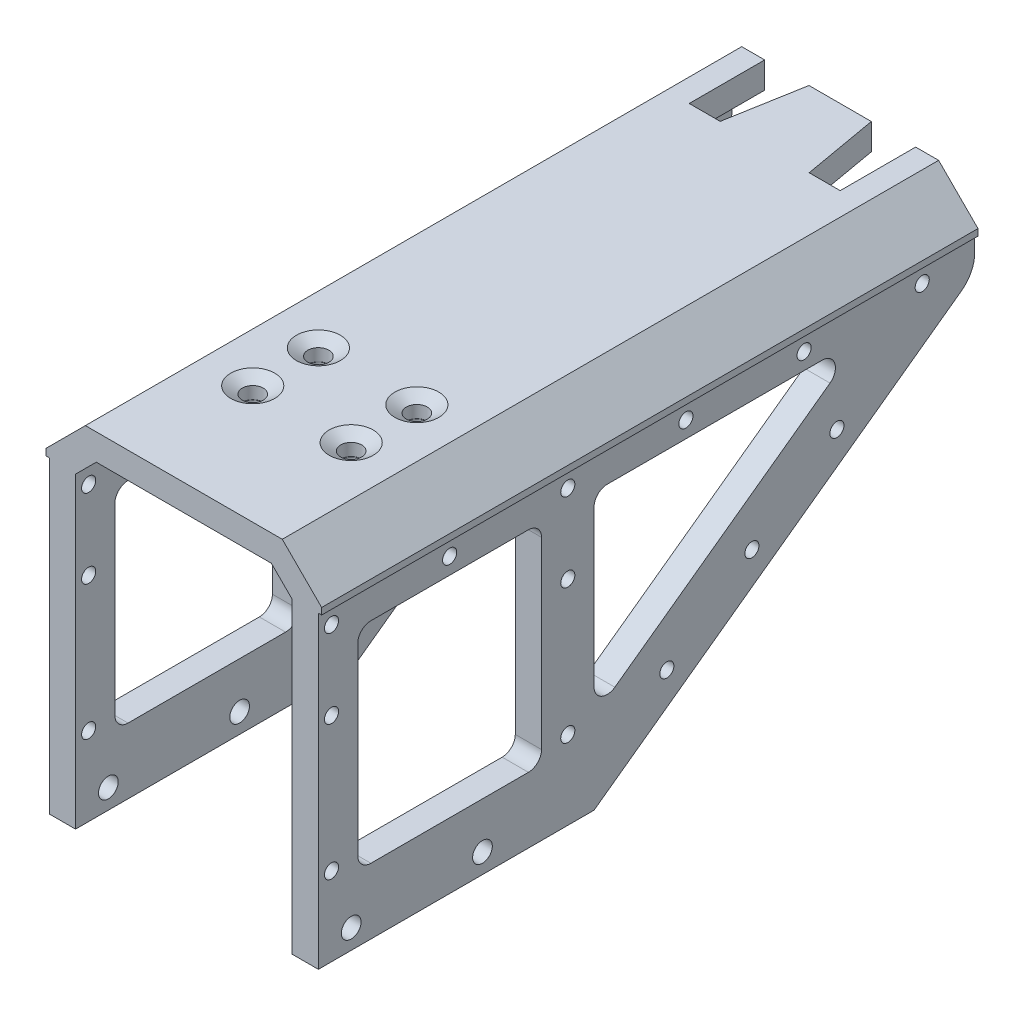
SolidWorks part; units mm, degrees
material "尼龙 101"
ref_plane "Front" through (0, 0, 0) normal (0, 0, 1) x (1, 0, 0)
ref_plane "Top" through (0, 0, 0) normal (0, 1, 0) x (1, 0, 0)
ref_plane "Right" through (0, 0, 0) normal (1, 0, 0) x (0, 0, -1)
sketch "草图1" plane through (0, 0, 0) normal (0, 0, 1) x (1, 0, 0)
  line L0 (0, 22.6301) -> (0, -19.2329) construction
  line L1 (-15, 0) -> (15, 0)
  line L3 (20.5, -54) -> (16.5, -54)
  line L5 (13.3431, -4) -> (-13.3431, -4)
  line L10 (16.5, -7.1569) -> (16.5, -54)
  line L12 (20.5, -7) -> (20.5, -54)
  line L18 (15, 0) -> (21, -6)
  line L19 (13.3431, -4) -> (16.5, -7.1569)
  line L20 (20.5, -7) -> (21, -7)
  line L21 (21, -7) -> (21, -6)
  line L22 (-21, -7) -> (-21, -6)
  line L23 (-20.5, -7) -> (-21, -7)
  line L24 (-13.3431, -4) -> (-16.5, -7.1569)
  line L25 (-15, 0) -> (-21, -6)
  line L26 (-20.5, -7) -> (-20.5, -54)
  line L27 (-16.5, -7.1569) -> (-16.5, -54)
  line L29 (-20.5, -54) -> (-16.5, -54)
  point P5 (0, 0)
  point P24 (0, -4)
  dimension "D5" = 4
  dimension "D6" = 4
  dimension "D1" = 47
  dimension "D2" = 0.5
  dimension "D3" = 50
  dimension "D4" = 15
  dimension "D7" = 135
  dimension "D8" = 4
  dimension "D9" = 16.5
extrude "凸台-拉伸1" add sketch "草图1" along normal mid plane 100
sketch "草图3" plane through (20.5, 0, 0) normal (1, 0, 0) x (0, 0, -1)
  line L0 (-8, -54) -> (50, -12)
  line L1 (-50, -54) -> (50, -54) construction
  line L2 (50, -54) -> (50, -7) construction
  line L3 (50, -12) -> (50, -54)
  line L4 (50, -54) -> (-8, -54)
  line L5 (-50, -54) -> (-50, -7) construction
  line L6 (-8, -41.6534) -> (-8, -54) construction
  line L17 (-50, -44) -> (50, -44)
  line L18 (-44, -44) -> (-16, -44)
  line L23 (-8, -41.6534) -> (32.95, -12)
  line L24 (-44, -54) -> (-44, -7)
  line L25 (-44, -44) -> (-44, -12)
  line L27 (-13.8651, -45.9006) -> (44.1349, -3.9006) construction
  line L28 (-50, -12) -> (50, -12)
  line L29 (-44, -12) -> (-16, -12)
  line L30 (-16, -44) -> (-16, -12)
  line L31 (-8, -41.6534) -> (-8, -12)
  line L32 (-8, -12) -> (32.95, -12)
  dimension "D1" = 42
  dimension "D2" = 5
  dimension "D7" = 8
  dimension "D3" = 10
  dimension "D4" = 6
  dimension "D5" = 10
  dimension "D6" = 5
extrude "切除-拉伸2" cut sketch "草图3" against normal through all
sketch "草图4" plane through (20.5, 0, 0) normal (1, 0, 0) x (0, 0, -1)
  line L0 (-50, -54) -> (-8, -54) construction
  line L1 (-50, -54) -> (-50, -7) construction
  line L2 (-50, -7) -> (50, -7) construction
  line L3 (50, -12) -> (-8, -54) construction
  line L4 (-30, -9.5) -> (-30, -50009.5) construction
  line L12 (-47, -51) -> (-8.9721, -51)
  line L13 (-8.9721, -51) -> (47, -10.4684)
  line L14 (47, -10.4684) -> (47, -10)
  line L15 (47, -10) -> (-47, -10)
  line L16 (-47, -10) -> (-47, -51)
  line L17 (-48, -51) -> (-10.6771, -51) construction
  line L33 (-10.6771, -51) -> (46.6324, -9.5) construction
  line L35 (46.6324, -9.5) -> (-48, -9.5) construction
  line L36 (-48, -9.5) -> (-48, -51) construction
  circle A0 centre (-45, -51) radius 1.5
  circle A1 centre (-25, -51) radius 1.5
  circle A2 centre (-48, -42) radius 1.075
  circle A3 centre (-48, -21.5) radius 1.075
  circle A4 centre (-48, -9.5) radius 1.075
  circle A12 centre (3.0919, -41.0293) radius 1.075
  circle A17 centre (-30, -9.5) radius 1.075
  circle A18 centre (-12, -9.5) radius 1.075
  circle A24 centre (6, -9.5) radius 1.075
  circle A27 centre (24, -9.5) radius 1.075
  circle A28 centre (42, -9.5) radius 1.075
  circle A29 centre (-12, -21.5) radius 1.075
  circle A30 centre (-12, -42) radius 1.075
  circle A31 centre (16.0509, -31.6452) radius 1.075
  circle A32 centre (29.01, -22.261) radius 1.075
  dimension "D1" = 3
  dimension "D2" = 3
  dimension "D3" = 5
  dimension "D4" = 20
  dimension "D5" = 3
  dimension "D7" = 2
  dimension "D10" = 6
  dimension "D11" = 9
  dimension "D12" = 3
  dimension "D14" = 2.15
  dimension "D16" = 16
  dimension "D18" = 17
  dimension "D8" = 2.5
  dimension "D9" = 4
  dimension "D13" = 12
  dimension "D15" = 18
  dimension "D6" = 3
extrude "切除-拉伸3" cut sketch "草图4" against normal through all
fillet "圆角1" radius 2 14 edges at (18.5, -12, -32.95) (18.5, -12, 16) (18.5, -12, 44) (18.5, -44, 44) (18.5, -44, 16) (18.5, -41.6534, 8) (-18.5, -12, 16) (18.5, -12, 8) (-18.5, -12, 8) (-18.5, -12, -32.95) (-18.5, -41.6534, 8) (-18.5, -12, 44) (-18.5, -44, 44) (-18.5, -44, 16)
sketch "草图8" plane through (20.5, 0, 0) normal (1, 0, 0) x (0, 0, -1)
  line L7 (-50, -18.6277) -> (-50, -24.3723)
  line L8 (-50, -7) -> (-50, -54) construction
  line L9 (-50, -39.1277) -> (-50, -44.8723)
  circle A7 centre (-48, -21.5) radius 1.5
  circle A9 centre (-48, -42) radius 1.5
  circle A10 centre (-12, -21.5) radius 3.5
  circle A11 centre (-12, -21.5) radius 1.5
  circle A12 centre (-12, -42) radius 3.5
  circle A13 centre (-12, -42) radius 1.5
  arc A20 (-50, -24.3723) -> (-50, -18.6277) centre (-48, -21.5) ccw
  arc A21 (-50, -44.8723) -> (-50, -39.1277) centre (-48, -42) ccw
  dimension "D2" = 7
  dimension "D3" = 3
  dimension "D4" = 7
  dimension "D5" = 3
  dimension "D6" = 7
  dimension "D7" = 3
  dimension "D8" = 3
  dimension "D15" = 7
extrude "凸台-拉伸4" add sketch "草图8" against normal blind 4
mirror "镜向2" about plane through (0, 0, 0) normal (1, 0, 0) of "凸台-拉伸4"
fillet "圆角4" radius 5 2 edges at (18.5, -12, -50) (-18.5, -12, -50)
sketch "草图10" plane through (0, 0, 0) normal (0, 1, 0) x (1, 0, 0)
  line L0 (-4.75, 50) -> (-6.7778, 38.5)
  line L1 (15, 50) -> (-15, 50) construction
  line L2 (-6.7778, 38.5) -> (-11.5, 38.5)
  line L3 (-11.5, 38.5) -> (-11.5, 50)
  line L4 (-11.5, 50) -> (-4.75, 50)
  line L5 (0, 50) -> (0, -49950) construction
  line L6 (11.5, 50) -> (4.75, 50)
  line L7 (11.5, 38.5) -> (11.5, 50)
  line L8 (6.7778, 38.5) -> (11.5, 38.5)
  line L9 (4.75, 50) -> (6.7778, 38.5)
  point P8 (0, 50)
  dimension "D1" = 9.5
  dimension "D2" = 100
  dimension "D3" = 23
  dimension "D4" = 11.5
extrude "切除-拉伸5" cut sketch "草图10" against normal blind 10
fillet "圆角7" [suppressed] radius 2
sketch "草图11" plane through (0, -4, 0) normal (0, -1, 0) x (1, 0, 0)
  line L0 (0, -10) -> (0, -20) construction
  line L1 (10, -10) -> (10, -20)
  line L2 (-10, -10) -> (-10, -20)
  line L3 (0, 30) -> (0, 20) construction
  line L4 (10, 30) -> (10, 20)
  line L5 (-10, 30) -> (-10, 20)
  arc A1 (10, -10) -> (-10, -10) centre (0, -10) ccw
  arc A2 (-10, -20) -> (10, -20) centre (0, -20) ccw
  arc A3 (10, 30) -> (-10, 30) centre (0, 30) ccw
  arc A4 (-10, 20) -> (10, 20) centre (0, 20) ccw
  point P2 (0, -15)
  point P8 (0, 25)
  dimension "D1" = 10
  dimension "D2" = 10
  dimension "D3" = 10
  dimension "D4" = 10
  dimension "D5" = 15
  dimension "D6" = 40
extrude "切除-拉伸6" [suppressed] cut sketch "草图11" against normal blind 2
fillet "圆角8" [suppressed] radius 1
sketch "草图12" plane through (0, 0, 0) normal (0, 1, 0) x (1, 0, 0)
  line L0 (15, -50) -> (-15, -50) construction
  line L1 (0, 0) -> (0, -58.0372) construction
  line L2 (-7.5, -32) -> (7.5, -32) construction
  line L3 (-7.5, -32) -> (-7.5, -22) construction
  line L4 (-7.5, -22) -> (7.5, -22) construction
  line L5 (7.5, -32) -> (7.5, -22) construction
  circle A0 centre (-7.5, -32) radius 1.6
  circle A1 centre (7.5, -32) radius 1.6
  circle A2 centre (7.5, -22) radius 1.6
  circle A3 centre (-7.5, -22) radius 1.6
  dimension "D1" = 18
  dimension "D4" = 3.2
  dimension "D2" = 10
  dimension "D3" = 15
extrude "切除-拉伸7" cut sketch "草图12" against normal through all
ref_plane "基准面1" through (0, -3, 0) normal (0, 1, 0) x (1, 0, 0)
sketch "草图13" plane through (0, 0, 0) normal (0, 1, 0) x (1, 0, 0)
  circle A0 centre (-7.5, -22) radius 3.35
  circle A1 centre (7.5, -22) radius 3.35
  circle A2 centre (-7.5, -32) radius 3.35
  circle A3 centre (7.5, -32) radius 3.35
  dimension "D1" = 6.7
sketch "草图14" plane through (0, -3, 0) normal (0, 1, 0) x (1, 0, 0)
  circle A0 centre (-7.5, -22) radius 1.65
  circle A1 centre (-7.5, -32) radius 1.65
  circle A2 centre (7.5, -32) radius 1.65
  circle A3 centre (7.5, -22) radius 1.65
  dimension "D1" = 3.3
loft "切除-放样1" cut section "草图13" section "草图14" start constraint default connector at (-10.0073, 0, 19.7783) connector at (-6.8533, -3, 23.518)
pattern_linear "阵列(线性)1" count 2 spacing 15 along (1, 0, 0) of "切除-放样1"
pattern_linear "阵列(线性)2" count 2 spacing 10 along (0, 0, 1) of "阵列(线性)1"
fillet "圆角9" [suppressed] radius 2.4
fillet "圆角10" [suppressed] radius 2.5
fillet "圆角11" [suppressed] radius 1.5
sketch "草图15" plane through (0, 0, 50) normal (0, 0, 1) x (1, 0, 0)
  line L0 (-16.5, -54) -> (-20.5, -54)
  line L1 (-20.5, -54) -> (-20.5, -7)
  line L2 (-20.5, -7) -> (-21, -7)
  line L3 (-21, -7) -> (-21, -6)
  line L4 (-21, -6) -> (-15, 0)
  line L5 (-15, 0) -> (15, 0)
  line L6 (15, 0) -> (21, -6)
  line L7 (21, -6) -> (15, 0) construction
  line L8 (21, -6) -> (21, -7)
  line L9 (21, -7) -> (20.5, -7)
  line L10 (20.5, -7) -> (20.5, -54)
  line L11 (20.5, -54) -> (20.5, -7) construction
  line L12 (20.5, -54) -> (16.5, -54)
  line L13 (16.5, -54) -> (16.5, -7.1569)
  line L14 (16.5, -7.1569) -> (13.3431, -4)
  line L15 (13.3431, -4) -> (-13.3431, -4)
  line L16 (-13.3431, -4) -> (-16.5, -7.1569)
  line L17 (-16.5, -7.1569) -> (-16.5, -54)
  line L18 (-15, 0) -> (-21, -6) construction
  dimension "D1" = 30
  dimension "D2" = 42
  dimension "D3" = 6
sketch "草图16" plane through (20.5, 0, 0) normal (1, 0, 0) x (0, 0, -1)
  line L0 (-42, -12) -> (-18, -12)
  line L1 (-44, -14) -> (-44, -42)
  line L2 (-42, -44) -> (-18, -44)
  line L3 (-16, -14) -> (-16, -42)
  line L4 (-16, -42) -> (-16, -14) construction
  line L5 (50, -9.4474) -> (50, -7)
  line L6 (50, -7) -> (-50, -7)
  line L7 (-50, -7) -> (-50, -54)
  line L8 (-50, -54) -> (-8, -54)
  line L9 (-8, -54) -> (47.9325, -13.4971)
  line L10 (50, -9.4474) -> (50, -7)
  line L11 (50, -7) -> (-50, -7)
  line L12 (-50, -7) -> (-50, -54)
  line L13 (-50, -54) -> (-8, -54)
  line L14 (-8, -54) -> (47.9325, -13.4971)
  line L15 (-8, -14) -> (-8, -37.7359)
  line L16 (-4.827, -39.3557) -> (27.9511, -15.6199)
  line L17 (-6, -12) -> (26.7781, -12)
  arc A0 (-44, -14) -> (-42, -12) centre (-42, -14) cw
  arc A1 (47.9325, -13.4971) -> (50, -9.4474) centre (45, -9.4474) ccw
  arc A2 (47.9325, -13.4971) -> (50, -9.4474) centre (45, -9.4474) ccw
  arc A3 (-18, -12) -> (-16, -14) centre (-18, -14) cw
  arc A4 (-44, -42) -> (-42, -44) centre (-42, -42) ccw
  arc A5 (-18, -44) -> (-16, -42) centre (-18, -42) ccw
  arc A6 (-6, -12) -> (-8, -14) centre (-6, -14) ccw
  arc A7 (26.7781, -12) -> (27.9511, -15.6199) centre (26.7781, -14) cw
  arc A8 (-8, -37.7359) -> (-4.827, -39.3557) centre (-6, -37.7359) ccw
  circle A9 centre (-48, -9.5) radius 1.075
  circle A10 centre (-30, -9.5) radius 1.075
  circle A11 centre (-12, -9.5) radius 1.075
  circle A12 centre (6, -9.5) radius 1.075
  circle A13 centre (24, -9.5) radius 1.075
  circle A14 centre (42, -9.5) radius 1.075
  circle A15 centre (29.01, -22.261) radius 1.075
  circle A16 centre (16.0509, -31.6452) radius 1.075
  circle A17 centre (3.0919, -41.0293) radius 1.075
  circle A18 centre (-12, -42) radius 1.075
  circle A19 centre (-12, -21.5) radius 1.075
  circle A20 centre (-25, -51) radius 1.5
  circle A21 centre (-45, -51) radius 1.5
  circle A25 centre (-48, -42) radius 1.075
  circle A26 centre (-48, -21.5) radius 1.075
  dimension "D2" = 2.15
  dimension "D3" = 3
  dimension "D1" = 0
sketch "草图17" [suppressed] plane through (0, 0, 50) normal (0, 0, 1) x (1, 0, 0)
  line L0 (0, 0) -> (-14.0059, 0)
  line L1 (-17.0029, -0.7029) -> (-22.3, -6)
  line L2 (-15.7029, -0.7029) -> (-21, -6)
  line L3 (-21, -6) -> (-21, -7)
  line L4 (-21, -7) -> (-20.5, -7)
  line L5 (-20.5, -7) -> (-20.5, -54)
  line L6 (-20.5, -54) -> (-16.5, -54)
  line L7 (-16.5, -54) -> (-16.5, -7.1569)
  line L8 (-16.5, -7.1569) -> (-13.3431, -4)
  line L9 (-13.3431, -4) -> (13.3431, -4)
  line L10 (13.3431, -4) -> (16.5, -7.1569)
  line L11 (16.5, -7.1569) -> (16.5, -54)
  line L12 (16.5, -54) -> (20.5, -54)
  line L13 (20.5, -54) -> (20.5, -7)
  line L14 (20.5, -7) -> (21, -7)
  line L15 (21, -7) -> (21, -6)
  line L16 (21, -7) -> (21, -6) construction
  line L17 (21, -6) -> (15.7029, -0.7029)
  line L18 (0, 0) -> (14.0059, 0)
  line L19 (-15.3059, 0) -> (-14.0059, 0)
  line L20 (-22.3, -6) -> (-22.3, -7)
  line L21 (-22.3, -7) -> (-21.8, -7)
  line L22 (-21.8, -7) -> (-21.8, -54)
  line L23 (-21.8, -54) -> (-20.5, -54)
  line L24 (0, 0) -> (0, -58.8568) construction
  line L25 (-15.7029, -0.7029) -> (-15, 0) construction
  line L26 (21.8, -54) -> (20.5, -54)
  line L27 (22.3, -7) -> (21.8, -7)
  line L28 (21.8, -7) -> (21.8, -54)
  line L29 (22.3, -6) -> (22.3, -7)
  line L30 (17.0029, -0.7029) -> (22.3, -6)
  line L31 (15.3059, 0) -> (14.0059, 0)
  arc A0 (-15.7029, -0.7029) -> (-14.0059, 0) centre (-14.0059, -2.4) cw
  arc A1 (14.0059, 0) -> (15.7029, -0.7029) centre (14.0059, -2.4) cw
  arc A2 (17.0029, -0.7029) -> (15.3059, 0) centre (15.3059, -2.4) ccw
  arc A3 (-15.3059, 0) -> (-17.0029, -0.7029) centre (-15.3059, -2.4) ccw
  point P56 (16.3, 0)
  point P59 (-16.3, 0)
  arc M29 (-14.0059, 0) -> (-15.7029, -0.7029) centre (-14.0059, -2.4) ccw
  line M30 (-15.7029, -0.7029) -> (-21, -6)
  line M31 (-21, -6) -> (-21, -7)
  line M32 (-21, -7) -> (-20.5, -7)
  line M33 (-20.5, -7) -> (-20.5, -54)
  line M41 (20.5, -54) -> (20.5, -7)
  line M42 (20.5, -7) -> (21, -7)
  line M43 (21, -7) -> (21, -6)
  line M44 (21, -6) -> (15.7029, -0.7029)
  arc M45 (15.7029, -0.7029) -> (14.0059, 0) centre (14.0059, -2.4) ccw
  dimension "D3" = 2.4
  dimension "D1" = 1.3
  dimension "D2" = 1.3
extrude "凸台-拉伸5" [suppressed] add sketch "草图17" against normal up to surface (100 mm away) contours L19 A3 L1 L20 L21 L22 L23 M33 M32 M31 M30 M29 | L30 A2 L31 L26 L28 L27 L29 M45 M44 M43 M42 M41 up to face at (-16.7343, -5.4052, -50)
sketch "草图18" [suppressed] plane through (21.8, 0, 0) normal (1, 0, 0) x (0, 0, -1)
  line L0 (47.9325, -13.4971) -> (-8, -54)
  line L1 (-8, -54) -> (50, -54)
  line L2 (50, -54) -> (50, -9.4474)
  arc A0 (47.9325, -13.4971) -> (50, -9.4474) centre (45, -9.4474) ccw
extrude "切除-拉伸8" [suppressed] cut sketch "草图18" against normal through all
sketch "草图19" [suppressed] plane through (21.8, 0, 0) normal (1, 0, 0) x (0, 0, -1)
  line L0 (-42, -12) -> (-18, -12)
  line L1 (-44, -14) -> (-44, -42)
  line L2 (-42, -44) -> (-18, -44)
  line L3 (-16, -14) -> (-16, -42)
  line L4 (-8, -14) -> (-8, -37.7359)
  line L5 (-4.827, -39.3557) -> (27.9511, -15.6199)
  line L6 (-6, -12) -> (26.7781, -12)
  arc A0 (-44, -14) -> (-42, -12) centre (-42, -14) cw
  arc A1 (-44, -42) -> (-42, -44) centre (-42, -42) ccw
  arc A2 (-18, -44) -> (-16, -42) centre (-18, -42) ccw
  arc A3 (-18, -12) -> (-16, -14) centre (-18, -14) cw
  arc A4 (-8, -14) -> (-6, -12) centre (-6, -14) cw
  arc A5 (-8, -37.7359) -> (-4.827, -39.3557) centre (-6, -37.7359) ccw
  arc A6 (26.7781, -12) -> (27.9511, -15.6199) centre (26.7781, -14) cw
  circle A7 centre (-48, -9.5) radius 1.075
  circle A8 centre (-48, -21.5) radius 1.075
  circle A9 centre (-48, -42) radius 1.075
  circle A10 centre (-45, -51) radius 1.5
  circle A11 centre (-25, -51) radius 1.5
  circle A12 centre (-12, -42) radius 1.075
  circle A13 centre (-12, -21.5) radius 1.075
  circle A14 centre (-30, -9.5) radius 1.075
  circle A15 centre (-12, -9.5) radius 1.075
  circle A16 centre (6, -9.5) radius 1.075
  circle A17 centre (24, -9.5) radius 1.075
  circle A18 centre (29.01, -22.261) radius 1.075
  circle A19 centre (42, -9.5) radius 1.075
  circle A20 centre (16.0509, -31.6452) radius 1.075
  circle A21 centre (3.0919, -41.0293) radius 1.075
  dimension "D1" = 2.15
  dimension "D2" = 3
extrude "切除-拉伸9" [suppressed] cut sketch "草图19" against normal through all
sketch "草图20" [suppressed] plane through (-21.8, 0, 0) normal (-1, 0, 0) x (0, 0, 1)
  line L5 (-47.9325, -13.4971) -> (8, -54)
  line L6 (8, -54) -> (50, -54)
  line L7 (50, -54) -> (50, -7)
  line L8 (50, -7) -> (-50, -7)
  line L9 (-50, -7) -> (-50, -9.4474)
  line L10 (-47.9325, -13.4971) -> (8, -54)
  line L11 (8, -54) -> (50, -54)
  line L12 (50, -54) -> (50, -7)
  line L13 (50, -7) -> (-50, -7)
  line L14 (-50, -7) -> (-50, -9.4474)
  arc A1 (-50, -9.4474) -> (-47.9325, -13.4971) centre (-45, -9.4474) ccw
  arc A2 (-50, -9.4474) -> (-47.9325, -13.4971) centre (-45, -9.4474) ccw
  dimension "D1" = 0
extrude "切除-拉伸10" [suppressed] cut sketch "草图20" against normal blind 1.5
sketch "草图21" [suppressed] plane through (21.8, 0, 0) normal (1, 0, 0) x (0, 0, -1)
  line L5 (-8, -54) -> (47.9325, -13.4971)
  line L6 (50, -9.4474) -> (50, -7)
  line L7 (50, -7) -> (-50, -7)
  line L8 (-50, -7) -> (-50, -54)
  line L9 (-50, -54) -> (-8, -54)
  line L10 (-8, -54) -> (47.9325, -13.4971)
  line L11 (50, -9.4474) -> (50, -7)
  line L12 (50, -7) -> (-50, -7)
  line L13 (-50, -7) -> (-50, -54)
  line L14 (-50, -54) -> (-8, -54)
  arc A1 (47.9325, -13.4971) -> (50, -9.4474) centre (45, -9.4474) ccw
  arc A2 (47.9325, -13.4971) -> (50, -9.4474) centre (45, -9.4474) ccw
  dimension "D1" = 0
extrude "切除-拉伸11" [suppressed] cut sketch "草图21" against normal blind 1.5
sketch "草图22" [suppressed] plane through (20.3, 0, 0) normal (1, 0, 0) x (0, 0, -1)
  line L0 (-50, -12) -> (49.2993, -12)
  line L1 (-42, -12) -> (-18, -12) construction
  line L5 (49.6797, -7) -> (-50, -7)
  line L6 (-50, -7) -> (-50, -54)
  line L7 (-50, -54) -> (-8, -54)
  line L8 (-8, -54) -> (47.9325, -13.4971)
  line L9 (50, -9.4474) -> (50, -8.6941)
  line L10 (49.6797, -7) -> (-50, -7)
  line L11 (-50, -7) -> (-50, -54)
  line L12 (-50, -54) -> (-8, -54)
  line L13 (-8, -54) -> (47.9325, -13.4971)
  line L14 (50, -9.4474) -> (50, -8.6941)
  arc A0 (47.9325, -13.4971) -> (50, -9.4474) centre (45, -9.4474) ccw construction
  arc A1 (47.9325, -13.4971) -> (50, -9.4474) centre (45, -9.4474) ccw
  arc A2 (47.9325, -13.4971) -> (50, -9.4474) centre (45, -9.4474) ccw
  ellipse E1 centre (47.6, -8.6941) end of major axis (47.6, -12.0882) minor radius 2.4 (50, -8.6941) -> (49.6797, -7) ccw
  ellipse E2 centre (47.6, -8.6941) end of major axis (47.6, -12.0882) minor radius 2.4 (50, -8.6941) -> (49.6797, -7) ccw
  arc M9 (26.7781, -12) -> (27.9511, -15.6199) centre (26.7781, -14) cw
  line M10 (27.9511, -15.6199) -> (-4.827, -39.3557)
  arc M11 (-4.827, -39.3557) -> (-8, -37.7359) centre (-6, -37.7359) cw
  line M12 (-8, -37.7359) -> (-8, -14)
  arc M13 (-8, -14) -> (-6, -12) centre (-6, -14) cw
  line M15 (-50, -7) -> (-50, -54)
  line M16 (-50, -54) -> (-8, -54)
  line M17 (-8, -54) -> (47.9325, -13.4971)
  arc M18 (47.9325, -13.4971) -> (50, -9.4474) centre (45, -9.4474) ccw
  arc M21 (-44, -14) -> (-42, -12) centre (-42, -14) cw
  arc M23 (-18, -12) -> (-16, -14) centre (-18, -14) cw
  line M24 (-16, -14) -> (-16, -42)
  arc M25 (-16, -42) -> (-18, -44) centre (-18, -42) cw
  line M26 (-18, -44) -> (-42, -44)
  arc M27 (-42, -44) -> (-44, -42) centre (-42, -42) cw
  line M28 (-44, -42) -> (-44, -14)
  circle M34 centre (-48, -21.5) radius 1.075
  circle M35 centre (-48, -42) radius 1.075
  circle M36 centre (-25, -51) radius 1.5
  circle M37 centre (29.01, -22.261) radius 1.075
  circle M38 centre (-12, -42) radius 1.075
  circle M39 centre (3.0919, -41.0293) radius 1.075
  circle M41 centre (16.0509, -31.6452) radius 1.075
  circle M42 centre (-12, -21.5) radius 1.075
  circle M43 centre (-45, -51) radius 1.5
  dimension "D1" = 0
extrude "切除-拉伸12" [suppressed] cut sketch "草图22" against normal through all and the other way through all contours L0 M15 M16 M17 M18 M9 M10 M11 M12 M13 M23 M24 M25 M26 M27 M28 M21 M35 M37 M39 M41 M43 M42 M38 M36 M34
sketch "草图23" [suppressed] plane through (20.3, 0, 0) normal (1, 0, 0) x (0, 0, -1)
  line L4 (-50, -7) -> (-50, -12)
  line L5 (-50, -12) -> (49.2993, -12)
  line L6 (50, -9.4474) -> (50, -8.6941)
  line L7 (49.6797, -7) -> (-50, -7)
  line L8 (-50, -7) -> (-50, -12)
  line L9 (-50, -12) -> (49.2993, -12)
  line L10 (50, -9.4474) -> (50, -8.6941)
  line L11 (49.6797, -7) -> (-50, -7)
  arc A1 (49.2993, -12) -> (50, -9.4474) centre (45, -9.4474) ccw
  arc A2 (49.2993, -12) -> (50, -9.4474) centre (45, -9.4474) ccw
  ellipse E1 centre (47.6, -8.6941) end of major axis (47.6, -12.0882) minor radius 2.4 (50, -8.6941) -> (49.6797, -7) ccw
  ellipse E2 centre (47.6, -8.6941) end of major axis (47.6, -12.0882) minor radius 2.4 (50, -8.6941) -> (49.6797, -7) ccw
  dimension "D1" = 0
extrude "切除-拉伸13" [suppressed] cut sketch "草图23" against normal blind 1
sketch "草图24" [suppressed] plane through (-20.3, 0, 0) normal (-1, 0, 0) x (0, 0, 1)
  line L4 (-49.2993, -12) -> (50, -12)
  line L5 (50, -12) -> (50, -7)
  line L6 (50, -7) -> (-49.6797, -7)
  line L7 (-50, -8.6941) -> (-50, -9.4474)
  line L8 (-49.2993, -12) -> (50, -12)
  line L9 (50, -12) -> (50, -7)
  line L10 (50, -7) -> (-49.6797, -7)
  line L11 (-50, -8.6941) -> (-50, -9.4474)
  arc A1 (-50, -9.4474) -> (-49.2993, -12) centre (-45, -9.4474) ccw
  arc A2 (-50, -9.4474) -> (-49.2993, -12) centre (-45, -9.4474) ccw
  ellipse E1 centre (-47.6, -8.6941) end of major axis (-47.6, -5.3) minor radius 2.4 (-49.6797, -7) -> (-50, -8.6941) ccw
  ellipse E2 centre (-47.6, -8.6941) end of major axis (-47.6, -5.3) minor radius 2.4 (-49.6797, -7) -> (-50, -8.6941) ccw
  dimension "D1" = 0
extrude "切除-拉伸14" [suppressed] cut sketch "草图24" against normal blind 1
sketch "草图25" plane through (0, 0, 50) normal (0, 0, 1) x (1, 0, 0)
  line L16 (-20.5, -7) -> (-20.5, -54)
  line L17 (-20.5, -7) -> (-20.5, -54)
  line L18 (-20.5, -54) -> (-16.5, -54)
  line L19 (-16.5, -54) -> (-16.5, -7.1569)
  line L20 (-16.5, -7.1569) -> (-13.3431, -4)
  line L21 (-13.3431, -4) -> (13.3431, -4)
  line L22 (13.3431, -4) -> (16.5, -7.1569)
  line L23 (16.5, -7.1569) -> (16.5, -54)
  line L24 (-20.5, -54) -> (-16.5, -54)
  line L25 (16.5, -54) -> (20.5, -54)
  line L26 (16.5, -54) -> (20.5, -54)
  line L27 (20.5, -54) -> (20.5, -7)
  line L28 (20.5, -54) -> (20.5, -7)
  line L29 (15, 0) -> (-15, 0)
  line L30 (20.5, -7) -> (21, -7)
  line L31 (20.5, -7) -> (21, -7)
  line L35 (-16.5, -54) -> (-16.5, -7.1569)
  line L36 (-16.5, -7.1569) -> (-13.3431, -4)
  line L37 (-13.3431, -4) -> (13.3431, -4)
  line L38 (13.3431, -4) -> (16.5, -7.1569)
  line L39 (16.5, -7.1569) -> (16.5, -54)
  line L45 (15, 0) -> (-15, 0)
  line L48 (21, -7) -> (21, -6)
  line L49 (21, -7) -> (21, -6)
  line L50 (21, -6) -> (15, 0)
  line L51 (21, -6) -> (15, 0)
  line L52 (-15, 0) -> (-21, -6)
  line L53 (-15, 0) -> (-21, -6)
  line L54 (-21, -6) -> (-21, -7)
  line L55 (-21, -6) -> (-21, -7)
  line L56 (-21, -7) -> (-20.5, -7)
  line L57 (-21, -7) -> (-20.5, -7)
  dimension "D1" = 0
